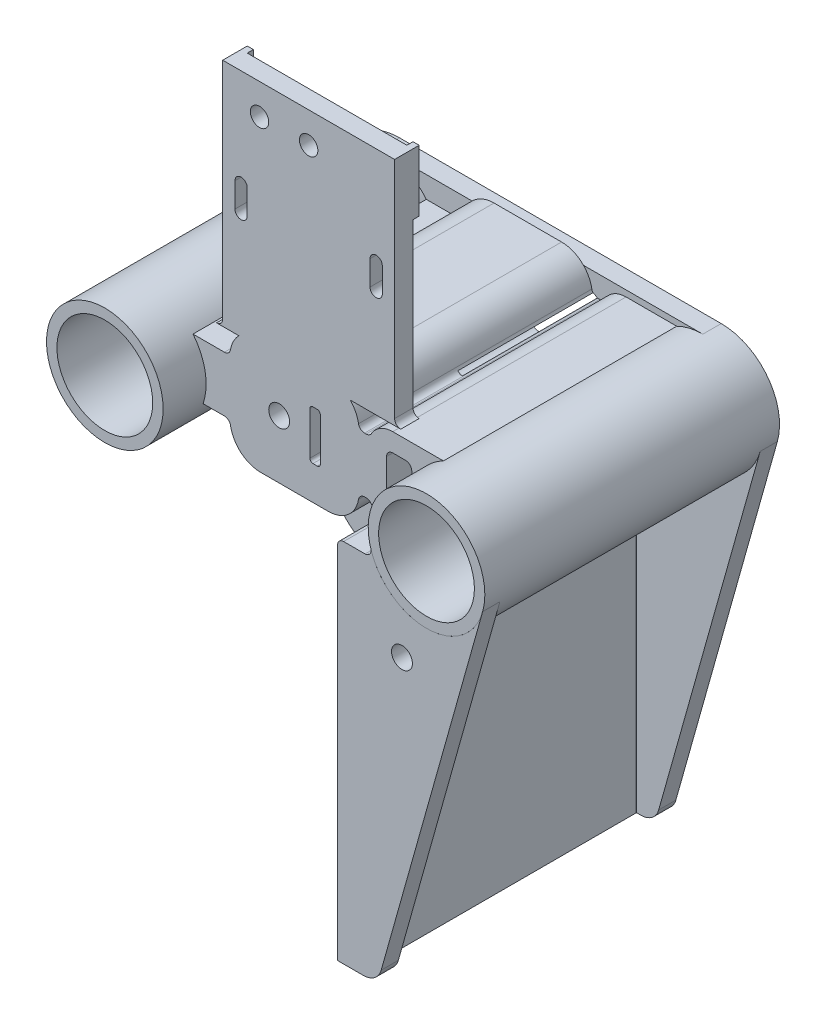
SolidWorks part; units mm, degrees
material "PET"
ref_plane "Front Plane" through (0, 0, 0) normal (0, 0, 1) x (1, 0, 0)
ref_plane "Top Plane" through (0, 0, 0) normal (0, 1, 0) x (1, 0, 0)
ref_plane "Right Plane" through (0, 0, 0) normal (1, 0, 0) x (0, 0, -1)
sketch "Sketch1" plane through (0, 0, 0) normal (0, 0, 1) x (1, 0, 0)
  circle A14 centre (0, 0) radius 7.8
  circle A15 centre (52.4, 0) radius 7.8
  circle A16 centre (0, 0) radius 9.5
  circle A17 centre (52.4, 0) radius 9.5
extrude "Boss-Extrude1" add sketch "Sketch1" along normal blind 48
sketch "Sketch29" plane through (0, 0, 0) normal (0, 0, -1) x (-1, 0, 0)
  line L6 (-52.4, 9.5) -> (0, 9.5)
  line L45 (9.5, -36.55) -> (9.5, 0)
  line L66 (-45.0149, -61.4114) -> (-61.5459, -2.5695)
  line L74 (-3.3, -49.35) -> (-31.9, -49.35)
  line L76 (-38.9, 4.5) -> (-38.9, -1.5)
  line L77 (-34.9, -52.35) -> (-34.9, -60.6)
  line L78 (-37.9, -63.6) -> (-42.1267, -63.6)
  line L80 (-43, -1.5) -> (-43, -1.3748)
  line L81 (-43, 1.3748) -> (-43, 4.5)
  line L82 (-39.9, 5.5) -> (-42, 5.5)
  line L84 (-39.9, -2.5) -> (-42, -2.5)
  circle A58 centre (-3.3, -36.55) radius 1.5
  circle A59 centre (-17.3, -36.55) radius 1.5
  arc A65 (0, 9.5) -> (9.5, 0) centre (0, 0) ccw
  arc A73 (-42.1267, -63.6) -> (-45.0149, -61.4114) centre (-42.1267, -60.6) cw
  arc A75 (9.5, -36.55) -> (-3.3, -49.35) centre (-3.3, -36.55) cw
  arc A87 (-31.9, -49.35) -> (-34.9, -52.35) centre (-31.9, -52.35) ccw
  arc A88 (-34.9, -60.6) -> (-37.9, -63.6) centre (-37.9, -60.6) cw
  arc A89 (-38.9, -1.5) -> (-39.9, -2.5) centre (-39.9, -1.5) cw
  arc A90 (-39.9, 5.5) -> (-38.9, 4.5) centre (-39.9, 4.5) cw
  arc A93 (-43, 4.5) -> (-42, 5.5) centre (-42, 4.5) cw
  arc A102 (-61.5459, -2.5695) -> (-43, -1.3748) centre (-52.4, 0) ccw
  arc A103 (-43, -1.5) -> (-42, -2.5) centre (-42, -1.5) ccw
  arc A104 (-43, 1.3748) -> (-52.4, 9.5) centre (-52.4, 0) ccw
extrude "Boss-Extrude18" add sketch "Sketch29" against normal blind 3
sketch "Sketch36" plane through (0, 0, 3) normal (0, 0, 1) x (1, 0, 0)
  line L9 (38.9, 4.5) -> (38.9, -1.5)
  line L15 (39.9, -2.5) -> (42, -2.5)
  line L17 (43, -1.5) -> (43, -1.3748)
  line L19 (43, 1.3748) -> (43, 4.5)
  line L20 (35.3161, -3) -> (35.5699, -3)
  line L21 (42, 5.5) -> (39.9, 5.5)
  line L22 (26.9, 5.5) -> (27.6, 5.5)
  line L23 (26.4, 5) -> (26.4, -2)
  line L24 (26.9, -2.5) -> (27.6, -2.5)
  line L25 (28.1, 5) -> (28.1, -2)
  line L34 (35.3161, 6) -> (35.5699, 6)
  line L35 (12.4839, 6) -> (7.3655, 6)
  line L36 (12.4839, -3) -> (9.0139, -3)
  line L39 (39.9, 8.5) -> (48.1574, 8.5)
  line L41 (18.4, 11) -> (29.4, 11)
  line L46 (18.4, -8) -> (29.4, -8)
  line L47 (39.9, -5.5) -> (44.654, -5.5)
  arc A0 (7.3655, 6) -> (9.0139, -3) centre (0, 0) cw
  arc A19 (39.9, 5.5) -> (38.9, 4.5) centre (39.9, 4.5) ccw
  arc A25 (38.9, -1.5) -> (39.9, -2.5) centre (39.9, -1.5) ccw
  arc A26 (42, -2.5) -> (43, -1.5) centre (42, -1.5) ccw
  arc A27 (43, 4.5) -> (42, 5.5) centre (42, 4.5) ccw
  arc A28 (43, -1.3748) -> (44.654, -5.5) centre (52.4, 0) ccw
  arc A29 (48.1574, 8.5) -> (43, 1.3748) centre (52.4, 0) ccw
  arc A30 (27.6, -2.5) -> (28.1, -2) centre (27.6, -2) ccw
  arc A31 (26.4, -2) -> (26.9, -2.5) centre (26.9, -2) ccw
  arc A32 (27.6, 5.5) -> (28.1, 5) centre (27.6, 5) cw
  arc A33 (26.9, 5.5) -> (26.4, 5) centre (26.9, 5) ccw
  circle A34 centre (21.4, 1.5) radius 1.7
  arc A43 (18.4, 11) -> (13.4699, 6.8333) centre (18.4, 6) ccw
  arc A46 (13.4699, -3.8333) -> (18.4, -8) centre (18.4, -3) ccw
  arc A53 (39.9, 8.5) -> (36.4359, 6.5) centre (39.9, 4.5) ccw
  arc A54 (36.4359, -3.5) -> (39.9, -5.5) centre (39.9, -1.5) ccw
  arc A55 (29.4, -8) -> (34.3301, -3.8333) centre (29.4, -3) ccw
  arc A57 (34.3301, 6.8333) -> (29.4, 11) centre (29.4, 6) ccw
  arc A58 (35.5699, -3) -> (36.4359, -3.5) centre (35.5699, -4) cw
  arc A59 (35.3161, -3) -> (34.3301, -3.8333) centre (35.3161, -4) ccw
  arc A60 (35.5699, 6) -> (36.4359, 6.5) centre (35.5699, 7) ccw
  arc A61 (35.3161, 6) -> (34.3301, 6.8333) centre (35.3161, 7) cw
  arc A62 (12.4839, 6) -> (13.4699, 6.8333) centre (12.4839, 7) ccw
  arc A63 (12.4839, -3) -> (13.4699, -3.8333) centre (12.4839, -4) cw
  point P9 (0, 0)
  point P34 (0, 0)
  point P35 (0, 0)
  point P40 (0, 0)
extrude "Boss-Extrude26" add sketch "Sketch36" along normal blind 38
sketch "Sketch14" plane through (0, -9.5, 0) normal (0, -1, 0) x (1, 0, 0)
  circle A2 centre (14.4, 28.5) radius 4.125
extrude "Boss-Extrude27" add sketch "Sketch14" along normal blind 4
sketch "Sketch34" plane through (0, 9.5, 0) normal (0, 1, 0) x (1, 0, 0)
  circle A4 centre (14.4, -28.5) radius 6
extrude "Cut-Extrude17" cut sketch "Sketch34" against normal blind 10 rebuild error yes
sketch "Sketch38" plane through (0, -0.5, 0) normal (0, 1, 0) x (1, 0, 0)
  circle A2 centre (14.5, -28.5) radius 2.15
extrude "Cut-Extrude18" cut sketch "Sketch38" against normal up to surface (13 mm away) rebuild error yes up to face at (18.525, -13.5, 28.5)
sketch "Sketch39" plane through (0, 0, 3) normal (0, 0, 1) x (1, 0, 0)
  line L12 (41.4, -63.6) -> (37.9, -63.6)
  line L13 (37.9, -5) -> (37.9, -63.6)
  line L17 (41.4, -63.6) -> (41.4, -9.5)
  line L19 (38.9, -4) -> (42.3861, -4)
  line L20 (41.4, -9.5) -> (52.4, -9.5)
  arc A2 (37.9, -5) -> (38.9, -4) centre (38.9, -5) cw
  arc A3 (42.3861, -4) -> (43.3861, -3) centre (42.3861, -3) ccw
  arc A5 (43.3861, -3) -> (52.4, -9.5) centre (52.4, 0) ccw
extrude "Boss-Extrude43" add sketch "Sketch39" along normal offset from surface (42.2 mm away) 2.8 up to face at (61.9, 0, 48)
sketch "Sketch7" plane through (0, 0, 45.2) normal (0, 0, 1) x (1, 0, 0)
  line L14 (37.9, -63.6) -> (42.1267, -63.6)
  line L19 (45.0149, -61.4114) -> (61.5459, -2.5695)
  line L21 (37.9, -5) -> (37.9, -63.6)
  line L25 (38.9, -4) -> (42.3861, -4)
  circle A4 centre (48.4, -15.6) radius 1.7
  arc A6 (42.1267, -63.6) -> (45.0149, -61.4114) centre (42.1267, -60.6) ccw
  arc A22 (38.9, -4) -> (37.9, -5) centre (38.9, -5) ccw
  arc A28 (43.3861, -3) -> (61.5459, -2.5695) centre (52.4, 0) ccw
  arc A29 (42.3861, -4) -> (43.3861, -3) centre (42.3861, -3) ccw
extrude "Boss-Extrude44" add sketch "Sketch7" along normal up to surface (2.8 mm away) up to face at (61.9, 0, 48)
sketch "Sketch69" plane through (37.9, 0, 0) normal (-1, 0, 0) x (0, 0, 1)
  line L0 (3, -9.5) -> (3, -25)
  line L2 (3, -25) -> (18.5, -9.5)
  line L4 (18.5, -9.5) -> (3, -9.5)
extrude "Boss-Extrude42" add sketch "Sketch69" along normal blind 6.5 from offset 25
sketch "Sketch40" plane through (0, 0, 45.2) normal (0, 0, -1) x (-1, 0, 0)
  line L23 (-42.2, -12.85) -> (-41.4, -12.85)
  line L24 (-42.2, -18.15) -> (-41.4, -18.15)
  line L26 (-41.4, -12.85) -> (-41.4, -18.15)
  line L28 (-42.7, -13.35) -> (-42.7, -17.65)
  arc A10 (-42.2, -12.85) -> (-42.7, -13.35) centre (-42.2, -13.35) ccw
  arc A11 (-42.7, -17.65) -> (-42.2, -18.15) centre (-42.2, -17.65) ccw
extrude "Boss-Extrude45" add sketch "Sketch40" along normal blind 10
sketch "Sketch47" plane through (41.4, 0, 0) normal (1, 0, 0) x (0, 0, -1)
  circle A0 centre (-8.5, -15.55) radius 1.5
  circle A1 centre (-8.5, -15.55) radius 4
extrude "Boss-Extrude40" add sketch "Sketch47" along normal blind 1.4
sketch "Sketch20" plane through (41.4, 0, 0) normal (1, 0, 0) x (0, 0, -1)
  circle A0 centre (-8.5, -58.1) radius 1.5
  circle A1 centre (-39.5, -58.1) radius 1.5
  circle A2 centre (-8.5, -27.1) radius 1.5
  circle A3 centre (-24, -42.6) radius 12.5
  circle A5 centre (-8.5, -15.55) radius 1.5
extrude "Cut-Extrude19" cut sketch "Sketch20" against normal up to surface (3.5 mm away) rebuild error yes up to face at (37.9, -34.3, 25.5)
sketch "Sketch43" plane through (0, 0, 41) normal (0, 0, 1) x (1, 0, 0)
  circle A1 centre (21.4, 1.5) radius 3.6
  point P2 (25.9, 1.5)
extrude "Cut-Extrude22" cut sketch "Sketch43" against normal blind 3.5 rebuild error yes
sketch "Sketch59" plane through (0, 0, 41) normal (0, 0, 1) x (1, 0, 0)
  line L20 (11.2, 9.5) -> (41.2, 9.5)
  line L28 (12.2, 10.5) -> (12.2, 47.05)
  line L29 (12.2, 47.05) -> (40.2, 47.05)
  line L30 (40.2, 47.05) -> (40.2, 10.5)
  arc A7 (11.2, 9.5) -> (12.2, 10.5) centre (11.2, 10.5) ccw
  arc A8 (40.2, 10.5) -> (41.2, 9.5) centre (41.2, 10.5) ccw
extrude "Boss-Extrude38" add sketch "Sketch59" against normal blind 3
sketch "Sketch52" plane through (-30, 0, 38) normal (0, 0, -1) x (-1, 0, 0)
  line L9 (-70.2, 47.05) -> (-69.2, 47.05)
  line L10 (-70.2, 47.05) -> (-70.2, 37.05)
  line L11 (-70.2, 37.05) -> (-69.2, 37.05)
  line L12 (-69.2, 47.05) -> (-69.2, 37.05)
  line L13 (-43.2, 47.05) -> (-42.2, 47.05)
  line L14 (-43.2, 47.05) -> (-43.2, 37.05)
  line L15 (-43.2, 37.05) -> (-42.2, 37.05)
  line L16 (-42.2, 47.05) -> (-42.2, 37.05)
extrude "Boss-Extrude36" add sketch "Sketch52" along normal blind 1
sketch "Sketch53" plane through (-30, 0, 38) normal (0, 0, -1) x (-1, 0, 0)
  line L15 (-68.2, 31.05) -> (-68.2, 27.05)
  line L17 (-66.2, 31.05) -> (-66.2, 27.05)
  line L29 (-46.2, 31.05) -> (-46.2, 27.05)
  line L30 (-44.2, 31.05) -> (-44.2, 27.05)
  circle A26 centre (-48.2, 42.05) radius 1.5
  circle A27 centre (-56.2, 42.05) radius 1.5
  arc A32 (-66.2, 31.05) -> (-68.2, 31.05) centre (-67.2, 31.05) ccw
  arc A33 (-68.2, 27.05) -> (-66.2, 27.05) centre (-67.2, 27.05) ccw
  arc A34 (-44.2, 31.05) -> (-46.2, 31.05) centre (-45.2, 31.05) ccw
  arc A35 (-46.2, 27.05) -> (-44.2, 27.05) centre (-45.2, 27.05) ccw
extrude "Cut-Extrude29" cut sketch "Sketch53" against normal up to surface (3 mm away) up to face at (31.322, 4.6009, 41)
sketch "Sketch62" plane through (0, 0, 3) normal (0, 0, 1) x (1, 0, 0)
  line L4 (61.9, -54.1) -> (61.9, 0)
  line L5 (52.4, -63.6) -> (41.4, -63.6)
  line L6 (41.4, -63.6) -> (41.4, -9.5)
  line L7 (41.4, -9.5) -> (52.4, -9.5)
  arc A1 (52.4, -9.5) -> (61.9, 0) centre (52.4, 0) ccw
  arc A2 (52.4, -63.6) -> (61.9, -54.1) centre (52.4, -54.1) ccw
extrude "Cut-Extrude30" cut sketch "Sketch62" against normal blind 0.2
sketch "Sketch70" plane through (0, 0, 0) normal (0, 0, -1) x (-1, 0, 0)
  line L2 (-33.9, -6.5) -> (-22.9, -6.5)
  line L3 (-20.9, -4.5) -> (-20.9, 4.5)
  line L4 (-22.9, 6.5) -> (-33.9, 6.5)
  line L5 (-35.9, 4.5) -> (-35.9, -4.5)
  arc A0 (-35.9, 4.5) -> (-33.9, 6.5) centre (-33.9, 4.5) cw
  arc A2 (-22.9, 6.5) -> (-20.9, 4.5) centre (-22.9, 4.5) cw
  arc A4 (-20.9, -4.5) -> (-22.9, -6.5) centre (-22.9, -4.5) cw
  arc A7 (-33.9, -6.5) -> (-35.9, -4.5) centre (-33.9, -4.5) cw
extrude "Cut-Extrude33" cut sketch "Sketch70" against normal blind 25
sketch "Sketch66" plane through (0, 0, 25) normal (0, 0, -1) x (-1, 0, 0)
  line L1 (-31.4, 4) -> (-32.9, 4)
  line L2 (-30.9, 3.5) -> (-30.9, -3.5)
  line L3 (-31.4, -4) -> (-32.9, -4)
  line L4 (-33.4, 3.5) -> (-33.4, -3.5)
  arc A0 (-30.9, -3.5) -> (-31.4, -4) centre (-31.4, -3.5) cw
  arc A1 (-32.9, -4) -> (-33.4, -3.5) centre (-32.9, -3.5) cw
  arc A2 (-32.9, 4) -> (-33.4, 3.5) centre (-32.9, 3.5) ccw
  arc A3 (-31.4, 4) -> (-30.9, 3.5) centre (-31.4, 3.5) cw
extrude "Cut-Extrude32" cut sketch "Sketch66" against normal blind 8
